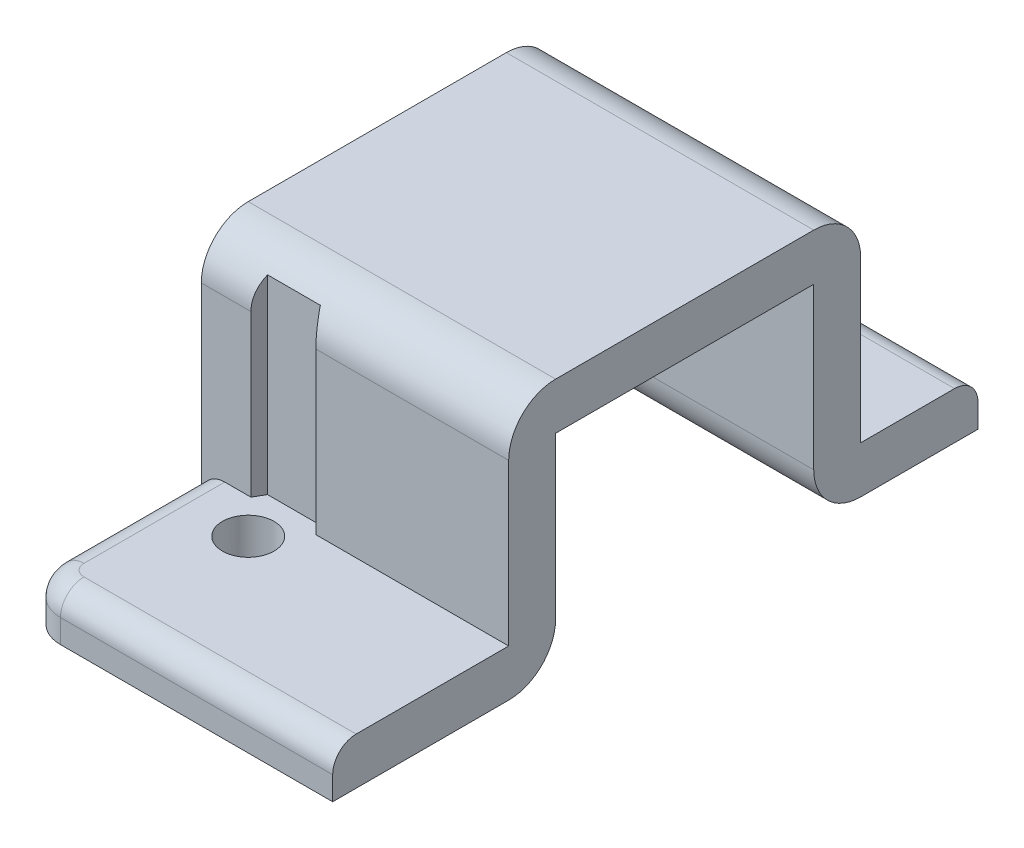
SolidWorks part; units mm, degrees
ref_plane "Front Plane" through (0, 0, 0) normal (0, 0, 1) x (1, 0, 0)
ref_plane "Top Plane" through (0, 0, 0) normal (0, 1, 0) x (1, 0, 0)
ref_plane "Right Plane" through (0, 0, 0) normal (1, 0, 0) x (0, 0, -1)
sketch "Sketch1" plane through (0, 0, 0) normal (1, 0, 0) x (0, 0, -1)
  line L0 (0, 55) -> (0, -55) construction
  line L3 (-5.5, 8.85) -> (5.5, 8.85)
  line L5 (-5.5, 10.85) -> (5.5, 8.85) construction
  line L6 (-5.5, 8.85) -> (5.5, 10.85) construction
  line L7 (55, 0) -> (-55, 0) construction
  line L9 (-5.5, 0) -> (-5.5, 8.85)
  line L10 (-7.5, 2) -> (-15, 2)
  line L11 (-15, 0) -> (-15, 2)
  line L12 (-7.5, 10.85) -> (7.5, 10.85)
  line L13 (7.5, 2) -> (12.5, 2)
  line L14 (5.5, 8.85) -> (5.5, 0)
  line L16 (12.5, 2) -> (12.5, 0)
  line L17 (-5.5, 0) -> (-15, 0)
  line L20 (-7.5, 2) -> (-7.5, 10.85)
  line L21 (5.5, 0) -> (12.5, 0)
  line L24 (7.5, 2) -> (7.5, 10.85)
  point P0 (0, 9.85)
  point P9 (0, 0)
  point P13 (0, 0)
  dimension "D1" = 9.5
  dimension "D2" = 11
  dimension "D3" = 2
  dimension "D4" = 2
  dimension "D5" = 2
  dimension "D6" = 7
  dimension "D7" = 2
  dimension "D8" = 6.85
  dimension "D9" = 2
extrude "Boss-Extrude1" add sketch "Sketch1" along normal mid plane 13.1 contours L13 L24 L20 L10 L11 L9 L3 L14 L16 region at (0, 4.425, 5.7956)
sketch "Sketch2" plane through (0, 2, 0) normal (0, 1, 0) x (1, 0, 0)
  line L1 (-6.55, -7.5) -> (-6.55, -15) construction
  line L2 (6.55, -15) -> (-6.55, -15) construction
  circle A0 centre (-3.05, -9) radius 1.1
  point P4 (0, 0)
  dimension "D3" = 2.2
  dimension "D1" = 3.5
  dimension "D2" = 6
extrude "Cut-Extrude1" cut sketch "Sketch2" against normal up to next
sketch "Sketch3" plane through (0, 2, 0) normal (0, 1, 0) x (1, 0, 0)
  line L1 (-5.3, -9) -> (-4.175, -10.9486)
  line L2 (-4.175, -10.9486) -> (-1.925, -10.9486)
  line L3 (-1.925, -10.9486) -> (-0.8, -9)
  line L4 (-0.8, -9) -> (-1.925, -7.0514)
  line L5 (-1.925, -7.0514) -> (-4.175, -7.0514)
  line L6 (-4.175, -7.0514) -> (-5.3, -9)
  line L9 (6.55, -15) -> (-6.55, -15) construction
  circle A0 centre (-3.05, -9) radius 2.25 construction
  circle A1 centre (-3.05, -9) radius 1.9486 construction
  point P3 (-3.55, -9.1)
  dimension "D1" = 4.5
extrude "Cut-Extrude2" cut sketch "Sketch3" along normal up to next
mirror "Mirror1" about plane through (0, 0, 0) normal (0, 0, 1) of "Cut-Extrude2", "Cut-Extrude1"
fillet "Fillet1" radius 2 4 edges at (0, 0, -5.5) (0, 0, 5.5) (2.442, 10.85, 7.5) (2.442, 10.85, -7.5)
fillet "Fillet3" radius 1.5 2 edges at (-6.55, 1, 15) (-6.55, 1, -12.5)
fillet "Fillet4" radius 1 6 edges at (-6.55, 2, 10.5) (-6.1107, 2, 14.5607) (-6.55, 2, -9.25) (-6.1107, 2, -12.0607) (0.75, 2, 15) (0.75, 2, -12.5)
